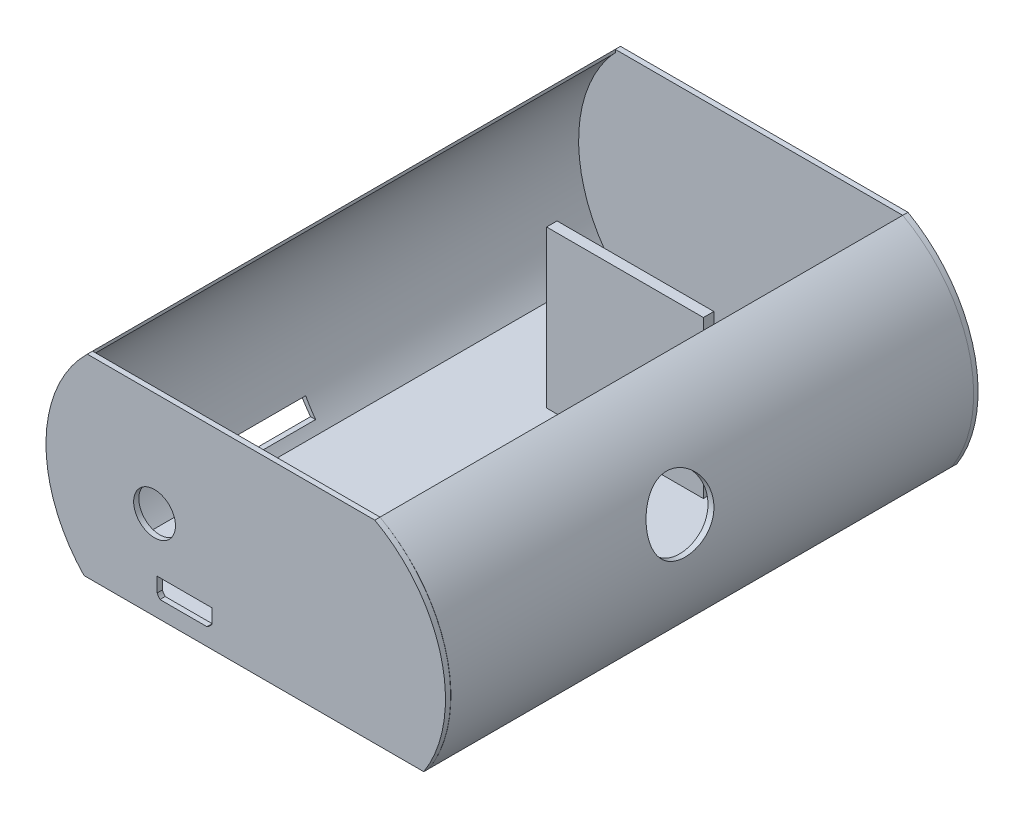
SolidWorks part; units mm, degrees
ref_plane "Front Plane" through (0, 0, 0) normal (0, 0, 1) x (1, 0, 0)
ref_plane "Top Plane" through (0, 0, 0) normal (0, 1, 0) x (1, 0, 0)
ref_plane "Right Plane" through (0, 0, 0) normal (1, 0, 0) x (0, 0, -1)
sketch "Sketch11" plane through (0, 0, 0) normal (0, 0, 1) x (1, 0, 0)
  line L0 (-50.9258, 31.4368) -> (4.0742, 31.4368)
  line L3 (13.439, -5.5632) -> (-51.561, -5.5632)
  line L4 (-51.013, 30.8355) -> (3.987, 30.8355)
  line L9 (3.987, 30.8355) -> (-51.013, 30.8355)
  line L11 (-51.561, -4.5645) -> (13.439, -4.5645)
  arc A0 (-50.9258, 31.4368) -> (-51.561, -5.5632) centre (-32.98, 12.6232) ccw
  arc A1 (4.0742, 31.4368) -> (13.439, -5.5632) centre (-8.3621, 8.604) cw
  arc A3 (-51.013, 30.8355) -> (-51.561, -4.5645) centre (-31.0337, 12.822) ccw
  arc A4 (3.987, 30.8355) -> (13.439, -4.5645) centre (-10.2712, 8.0666) cw
  point P6 (-46.0039, -5.5632)
  point P7 (0, 0)
  point P8 (4.0848, 31.4053)
  point P9 (0, 0)
  point P10 (0, 0)
  point P11 (-50.9306, 31.4107)
  point P12 (-50.9258, 31.4053)
  point P13 (0, 0)
  point P14 (-50.4849, -5.5242)
  point P16 (-42.4967, -7.8635)
  point P21 (-51.5322, -5.5126)
  point P23 (-51.561, -4.5645)
  dimension "D3" = 26
  dimension "D4" = 65
  dimension "D5" = 55
  dimension "D6" = 37
  dimension "D7" = 65
  dimension "D9" = 0.9987
  dimension "D18" = 55
  dimension "D23" = 35.4
extrude "Boss-Extrude6" add sketch "Sketch11" along normal blind 100 and the other way blind 0.001 contours A1 L0 A0 L3 L4 A4 L11 A3 region at (-23.4258, 31.3517, 0)
ref_plane "front" through (0, 0, 100) normal (0, 0, 1) x (1, 0, 0)
ref_plane "Plane9" through (0, 31.4368, 0) normal (0, -1, 0) x (-1, 0, 0)
sketch "Buttons" plane through (0, 31.4368, 0) normal (0, -1, 0) x (-1, 0, 0)
  line L5 (50.7065, 0.001) -> (-4.2935, 0.001)
  line L6 (50.7065, 0.001) -> (50.7065, -99.999)
  line L7 (50.7065, -99.999) -> (-4.2935, -99.999)
  line L8 (-4.2935, 0.001) -> (-4.2935, -99.999)
  line L10 (-13.439, 0.001) -> (51.561, 0.001) construction
  dimension "D3" = 0
  dimension "D11" = 55
  dimension "D12" = 100
ref_plane "Plane5" through (17.6379, 0, 0) normal (1, 0, 0) x (0, 0, -1)
sketch "Sketch19" plane through (17.6379, 0, 0) normal (1, 0, 0) x (0, 0, -1)
  line L2 (-100, 31.4368) -> (-100, -5.5632) construction
  line L3 (0.001, -5.5632) -> (-100, -5.5632) construction
  circle A0 centre (-55.2, 15.4368) radius 6.25
  dimension "D1" = 21
  dimension "D3" = 12.5
  dimension "D2" = 44.8
extrude "side button" cut sketch "Sketch19" against normal blind 10
ref_plane "sd card" through (-58.98, 0, 0) normal (-1, 0, 0) x (0, 0, 1)
sketch "Sketch21" plane through (-58.98, 0, 0) normal (-1, 0, 0) x (0, 0, 1)
  line L0 (55.5, -0.0632) -> (68.5, -0.0632)
  line L1 (55.5, -0.0632) -> (55.5, -3.0632)
  line L2 (55.5, -3.0632) -> (68.5, -3.0632)
  line L3 (68.5, -0.0632) -> (68.5, -3.0632)
  line L4 (100, -5.5632) -> (100, 31.4368) construction
  line L6 (-0.001, -5.5632) -> (100, -5.5632) construction
  dimension "D1" = 44.5
  dimension "D2" = 3
  dimension "D3" = 5.5
  dimension "D9" = 13
extrude "sd" cut sketch "Sketch21" against normal blind 10
ref_plane "for top cover layer" through (0, 0, -0.001) normal (0, 0, -1) x (-1, 0, 0)
ref_plane "top exclusive" through (0, 31.4368, 0) normal (0, 1, 0) x (1, 0, 0)
sketch "草图4" plane through (0, 0, 100) normal (0, 0, 1) x (1, 0, 0)
  line L0 (-50.9258, 31.4368) -> (4.0742, 31.4368)
  line L1 (13.439, -5.5632) -> (-51.561, -5.5632)
  line L2 (-37.561, 1.3328) -> (-27.1017, 1.3328)
  line L3 (-37.561, 1.3328) -> (-37.561, -1.4468)
  line L4 (-27.1017, 1.3328) -> (-27.1017, -1.4468)
  line L5 (-37.0287, -2.2713) -> (-28.0296, -2.2713)
  arc A0 (-50.9258, 31.4368) -> (-51.561, -5.5632) centre (-32.4656, 12.6144) ccw
  arc A1 (4.0742, 31.4368) -> (13.439, -5.5632) centre (-8.5033, 8.5682) cw
  circle A2 centre (-38.061, 11.4368) radius 4
  arc A3 (-37.561, -1.4468) -> (-37.0287, -2.2713) centre (-34.7289, -0.2026) ccw
  arc A4 (-27.1017, -1.4468) -> (-28.0296, -2.2713) centre (-29.5318, 0.3535) cw
  point P6 (-47.4797, -5.5632)
  point P11 (-38.061, 7.4368)
  point P12 (-42.061, 11.4368)
  point P19 (-50.9152, 31.3935)
  point P20 (-50.9152, 20.1955)
  point P21 (-51.1687, 30.8466)
  point P22 (-50.6508, 31.1955)
  point P23 (-50.5496, -5.6065)
  point P24 (-36.8496, 15.2721)
  point P25 (0, 0)
  point P26 (0, 0)
  point P28 (-50.9152, 20.1955)
  point P30 (0, 0)
  point P31 (0, 0)
  point P32 (-35.446, -3.7518)
  point P33 (-28.0106, -3.9863)
  point P34 (-36.6068, -3.1618)
  point P35 (12.0848, 31.3935)
  point P36 (4.5151, -5.5242)
  point P37 (4.5151, -5.5242)
  point P38 (4.8425, -5.5242)
  point P39 (4.5151, -5.5242)
  point P41 (0, 0)
  dimension "D3" = 8
  dimension "D1" = 65
  dimension "D2" = 55
  dimension "D4" = 17
  dimension "D5" = 14
  dimension "D6" = 13.5
sketch "草图5" plane through (0, 31.4368, 0) normal (0, 1, 0) x (1, 0, 0)
  line L1 (-50.9258, 0.001) -> (4.0742, 0.001)
  line L2 (-50.9258, 0.001) -> (-50.9258, -100)
  line L3 (-50.9258, -100) -> (4.0742, -100)
  line L4 (4.0742, 0.001) -> (4.0742, -100)
extrude "切除-拉伸4" cut sketch "草图5" against normal blind 7
extrude "ports" add sketch "草图4" along normal blind 1
sketch "草图6" plane through (0, 0, -0.001) normal (0, 0, -1) x (-1, 0, 0)
  line L0 (-4.0742, 31.4368) -> (50.9258, 31.4368)
  line L1 (51.561, -5.5632) -> (-13.439, -5.5632)
  arc A0 (-4.0742, 31.4368) -> (-13.439, -5.5632) centre (8.8775, 8.4735) ccw
  arc A1 (50.9258, 31.4368) -> (51.561, -5.5632) centre (32.8392, 12.6208) cw
  point P6 (-8.649, -5.5632)
  point P7 (0, 0)
  point P8 (0, 0)
  point P9 (0, 0)
  point P10 (0, 0)
  point P11 (-4.0742, 31.4758)
  point P19 (0, 0)
  point P20 (-12.4504, -5.6065)
  point P22 (-12.1029, 31.3631)
  dimension "D1" = 65
  dimension "D2" = 55
extrude "top cover " add sketch "草图6" along normal blind 1
ref_plane "inner obstacle" through (0, -4.5645, 0) normal (0, 1, 0) x (1, 0, 0)
sketch "草图7" plane through (0, -4.5645, 0) normal (0, 1, 0) x (1, 0, 0)
  line L0 (-51.561, -100) -> (13.439, -100) construction
  line L1 (-34.061, -28) -> (-4.061, -28)
  line L2 (-34.061, -28) -> (-34.061, -30)
  line L3 (-34.061, -30) -> (-4.061, -30)
  line L4 (-4.061, -28) -> (-4.061, -30)
  line L5 (-51.561, 0.001) -> (-51.561, -100) construction
  dimension "D1" = 30
  dimension "D2" = 2
  dimension "D3" = 70
  dimension "D4" = 17.5
extrude "凸台-拉伸5" add sketch "草图7" along normal blind 30
